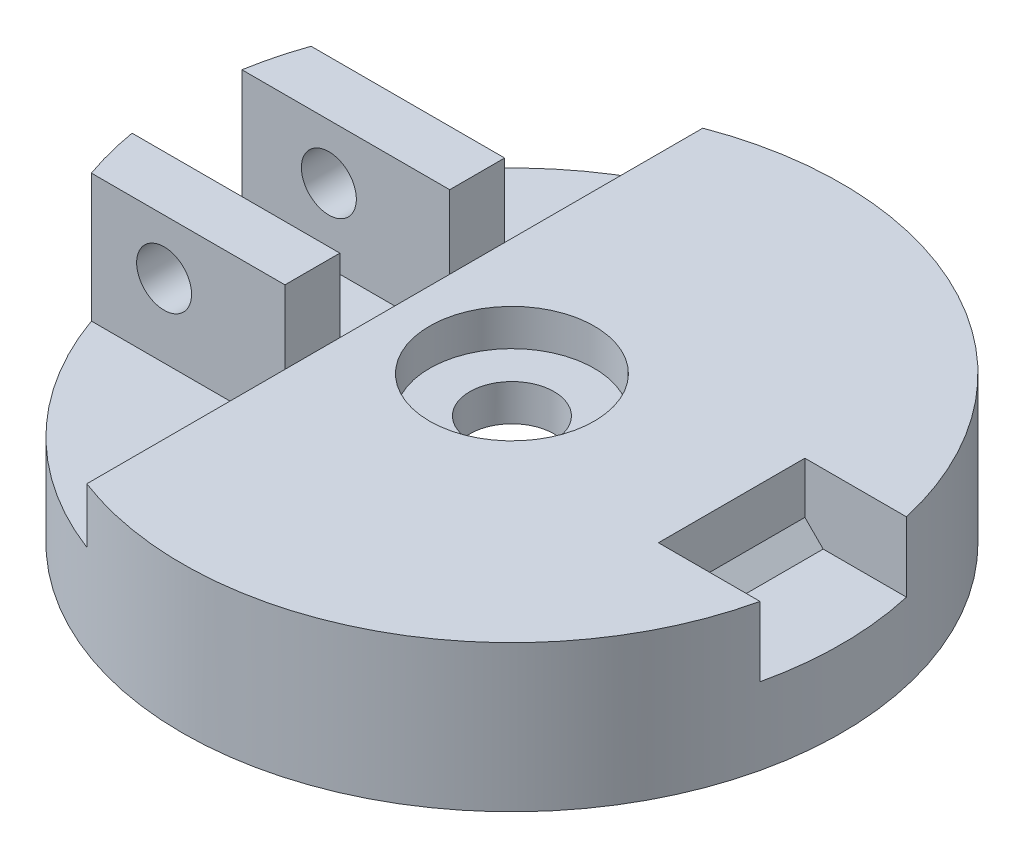
SolidWorks part; units mm, degrees
ref_plane "Front Plane" through (0, 0, 0) normal (0, 0, 1) x (1, 0, 0)
ref_plane "Top Plane" through (0, 0, 0) normal (0, 1, 0) x (1, 0, 0)
ref_plane "Right Plane" through (0, 0, 0) normal (1, 0, 0) x (0, 0, -1)
sketch "Sketch1" plane through (0, 0, 0) normal (0, 1, 0) x (1, 0, 0)
  circle A0 centre (0, 0) radius 9
  dimension "D1" = 18
extrude "Boss-Extrude1" add sketch "Sketch1" along normal blind 6
sketch "Sketch2" plane through (0, 6, 0) normal (0, 1, 0) x (1, 0, 0)
  circle A0 centre (0, 0) radius 1.15
  dimension "D1" = 2.3
extrude "Cut-Extrude1" cut sketch "Sketch2" against normal through all
sketch "Sketch5" plane through (0, 6, 0) normal (0, 1, 0) x (1, 0, 0)
  line L1 (-3.2, 3) -> (-8.4853, 3)
  line L2 (-3.2, 3) -> (-3.2, 8.4119)
  line L3 (-3.2, 8.4119) -> (-8.4853, 8.4119)
  line L4 (-8.4853, 3) -> (-8.4853, 8.4119)
  circle A2 centre (0, 0) radius 9 construction
  dimension "D1" = 3.2
  dimension "D2" = 3
extrude "Cut-Extrude3" cut sketch "Sketch5" against normal blind 3.5
mirror "Mirror1" about plane through (0, 0, 0) normal (0, 0, 1) of "Cut-Extrude3"
sketch "Sketch6" plane through (0, 6, 0) normal (0, 1, 0) x (1, 0, 0)
  line L0 (-3.2, -3) -> (-3.2, -8.4119) construction
  line L1 (-3.2, 9) -> (23.0525, 9)
  line L2 (-3.2, 9) -> (-3.2, -20.0526)
  line L3 (-3.2, -20.0526) -> (23.0525, -20.0526)
  line L4 (23.0525, 9) -> (23.0525, -20.0526)
  arc A0 (-3.2, -8.4119) -> (-3.2, 8.4119) centre (0, 0) ccw construction
extrude "Cut-Extrude4" cut sketch "Sketch6" against normal blind 2
sketch "Sketch7" plane through (0, 6, 0) normal (0, 1, 0) x (1, 0, 0)
  line L0 (-3.2, 3) -> (-3.2, -3) construction
  line L1 (-3.2, -1.5) -> (-12.173, -1.5)
  line L2 (-3.2, -1.5) -> (-3.2, 1.5)
  line L3 (-3.2, 1.5) -> (-12.173, 1.5)
  line L4 (-12.173, -1.5) -> (-12.173, 1.5)
  dimension "D1" = 1.5
  dimension "D2" = 3
extrude "Cut-Extrude5" cut sketch "Sketch7" against normal blind 3.5
sketch "Sketch10" plane through (0, 4, 0) normal (0, 1, 0) x (1, 0, 0)
  circle A0 centre (0, 0) radius 2.25
  dimension "D1" = 4.5
extrude "Cut-Extrude6" cut sketch "Sketch10" against normal blind 1
sketch "Sketch11" plane through (0, 0, 0) normal (0, -1, 0) x (1, 0, 0)
  circle A0 centre (0, 0) radius 6
  dimension "D1" = 12
extrude "Cut-Extrude7" cut sketch "Sketch11" against normal blind 2
sketch "Sketch12" plane through (0, 4, 0) normal (0, 1, 0) x (1, 0, 0)
  line L1 (6, -2) -> (11.6408, -2)
  line L2 (6, -2) -> (6, 2)
  line L3 (6, 2) -> (11.6408, 2)
  line L4 (11.6408, -2) -> (11.6408, 2)
  arc A0 (-3.2, -8.4119) -> (-3.2, 8.4119) centre (0, 0) ccw construction
  dimension "D1" = 6
  dimension "D2" = 2
  dimension "D3" = 2
extrude "Cut-Extrude8" cut sketch "Sketch12" against normal blind 1.9
hole_wizard "Ø1.5 (1.5) Diameter Hole1" positions "Sketch8" profile "Sketch9" hole size "Ø1.5" standard "DIN" end condition through all
sketch "Sketch8" plane through (0, 0, -3) normal (0, 0, -1) x (-1, 0, 0)
  line L0 (8.4853, 6) -> (3.2, 6) construction
  point P0 (6.5, 4.5)
  dimension "D1" = 1.5
  dimension "D2" = 6.5
sketch "Sketch9" plane through (-6.5, 4.5, -3) normal (1, 0, 0) x (0, 1, 0)
  line L0 (0, 0) -> (0, 12)
  line L1 (0, 12) -> (0.75, 12)
  line L2 (0.75, 12) -> (0.75, 0)
  line L5 (0.75, 0) -> (0, 0)
  line L11 (0, -6.35) -> (0, 107.95) construction
  dimension "Thru Hole Dia." = 1.5
  dimension "Thru Hole Depth" = 12
fillet "Fillet7" radius 0.5 1 edges at (0, 2, -6) type face fillet first side face at (0, 2, -6) second side face at (0, 2, -6)
sketch "Sketch16" plane through (0, 0, 2) normal (0, 0, -1) x (-1, 0, 0)
  line L0 (-6, 2.1) -> (-6.5, 2.1)
  line L1 (-6, 2.1) -> (-8.775, 2.1) construction
  line L2 (-6.5, 2.1) -> (-6, 2.6)
  line L3 (-6, 2.1) -> (-6, 4) construction
  line L4 (-6, 2.6) -> (-6, 2.1)
  dimension "D1" = 0.5
  dimension "D2" = 0.5
extrude "Boss-Extrude4" add sketch "Sketch16" along normal up to surface (4 mm away) up to face at (7.3875, 3.05, -2)
equation "\"D2@Sketch7\"=\"D1@Sketch7\"*2"
equation "\"D3@Sketch12\"=\"D2@Sketch12\""
equation "\"D2@Sketch16\"=.5"
